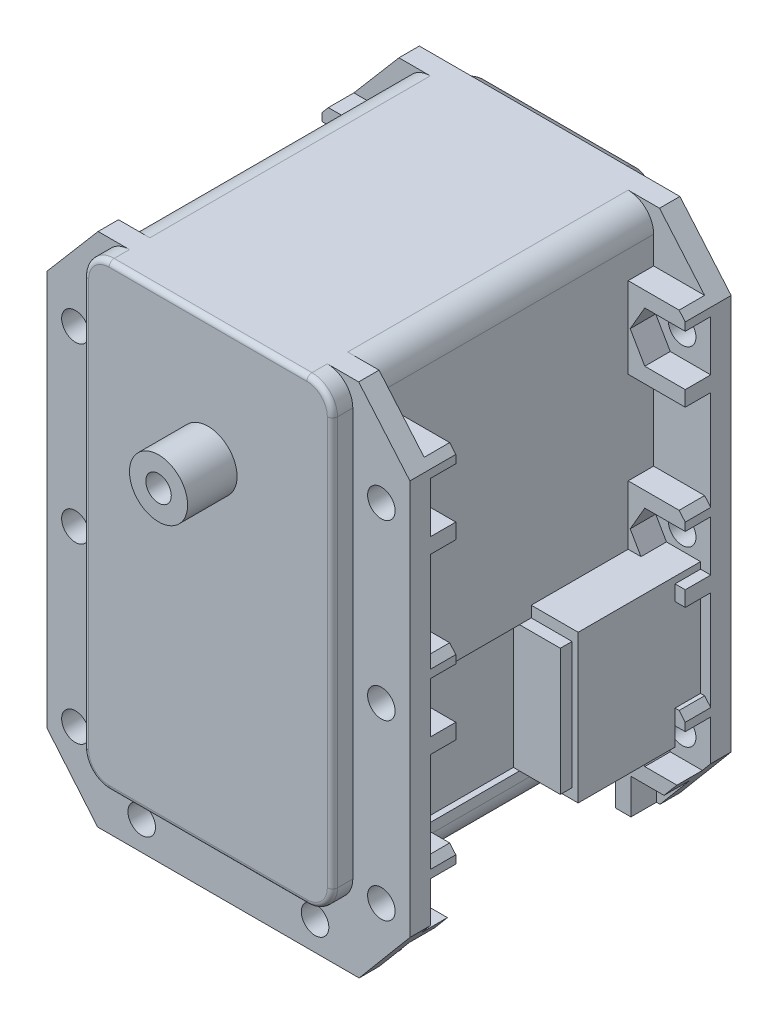
SolidWorks part; units mm, degrees
ref_plane "Ön Düzlem" through (0, 0, 0) normal (0, 0, 1) x (1, 0, 0)
ref_plane "Üst Düzlem" through (0, 0, 0) normal (0, 1, 0) x (1, 0, 0)
ref_plane "Sağ Düzlem" through (0, 0, 0) normal (1, 0, 0) x (0, 0, -1)
sketch "Sketch1" plane through (0, 0, 0) normal (0, 0, 1) x (1, 0, 0)
  line L1 (-12.2, 22.5) -> (12.2, 22.5)
  line L2 (-12.2, 22.5) -> (-12.2, -22.5)
  line L3 (-12.2, -22.5) -> (12.2, -22.5)
  line L4 (12.2, 22.5) -> (12.2, -22.5)
  line L5 (-12.2, 22.5) -> (12.2, -22.5) construction
  line L6 (-12.2, -22.5) -> (12.2, 22.5) construction
  point P0 (0, 0)
  dimension "D1" = 45
  dimension "D2" = 24.4
extrude "Boss-Extrude1" add sketch "Sketch1" along normal mid plane 35.5
ref_plane "Plane1" through (0, 0, 15.75) normal (0, 0, 1) x (1, 0, 0)
sketch "Sketch2" plane through (0, 0, 15.75) normal (0, 0, 1) x (1, 0, 0)
  line L1 (-12.7753, 22.5) -> (-17.8, 16.6036)
  line L2 (-17.8, 16.6036) -> (-17.8, -22.1655)
  line L3 (-17.8, -22.1655) -> (-12.8203, -28.1)
  line L4 (-12.8203, -28.1) -> (12.8203, -28.1)
  line L5 (12.8203, -28.1) -> (17.8, -22.1655)
  line L6 (17.8, -22.1655) -> (17.8, 16.6036)
  line L7 (17.8, 16.6036) -> (12.7753, 22.5)
  line L8 (12.7753, 22.5) -> (-12.7753, 22.5)
  line L9 (0, 0) -> (0, -28.1) construction
  line L10 (12.2, -22.5) -> (12.2, 22.5) construction
  line L11 (-12.2, -22.5) -> (12.2, -22.5) construction
  line L14 (12.2, 22.5) -> (-12.2, 22.5) construction
  circle A0 centre (15, 13.3345) radius 1.35
  circle A1 centre (15, -3.6655) radius 1.35
  circle A2 centre (15, -20.6655) radius 1.35
  circle A3 centre (8.5, -25.3) radius 1.35
  circle A4 centre (-8.5, -25.3) radius 1.35
  circle A5 centre (-15, -20.6655) radius 1.35
  circle A6 centre (-15, 13.3345) radius 1.35
  circle A7 centre (-15, -3.6655) radius 1.35
  dimension "D9" = 15
  dimension "D8" = 2.7
  dimension "D1" = 35.6
  dimension "D2" = 220
  dimension "D3" = 5.9345
  dimension "D4" = 5.6
  dimension "D5" = 17
  dimension "D6" = 17
  dimension "D7" = 220.437
  dimension "D10" = 8.5
  dimension "D11" = 1.5
  dimension "D12" = 2.8
extrude "Boss-Extrude2" add sketch "Sketch2" against normal blind 2 separate body
sketch "Sketch4" plane through (0, 0, 13.75) normal (0, 0, -1) x (-1, 0, 0)
  line L0 (12.2, 22.5) -> (12.2, -22.5) construction
  line L1 (17.8, 9.3595) -> (12.2, 9.3595)
  line L2 (17.8, 9.3595) -> (17.8, 17.3095)
  line L3 (17.8, 17.3095) -> (12.2, 17.3095)
  line L4 (12.2, 9.3595) -> (12.2, 17.3095)
  line L5 (17.8, 9.3595) -> (12.2, 17.3095) construction
  line L6 (17.8, 17.3095) -> (12.2, 9.3595) construction
  line L7 (17.8, 15.8095) -> (13.83, 15.8095)
  line L8 (13.83, 15.8095) -> (12.4, 13.3345)
  line L9 (12.4, 13.3345) -> (13.83, 10.8595)
  line L10 (13.83, 10.8595) -> (17.8, 10.8595)
  line L11 (15, 13.3345) -> (17.8, 13.3345) construction
  point P0 (15, 13.3345)
  point P6 (15, 13.3345)
  line M16 (17.8, -22.1655) -> (17.8, 16.6036)
  line M17 (17.8, 16.6036) -> (12.7753, 22.5)
  dimension "D1" = 7.95
  dimension "D2" = 4.95
  dimension "D3" = 1.43
  dimension "D4" = 0.2
extrude "Boss-Extrude6" add sketch "Sketch4" along normal blind 2.5 contours L10 L9 L8 L7 L2 L3 L4 L1 M17 M16 region at (-15, 9.4568, 13.75)
pattern_linear "LPattern1" count 3 spacing 17 along (0, -1, 0) of "Boss-Extrude6"
sketch "Sketch6" plane through (0, 0, 13.75) normal (0, 0, -1) x (-1, 0, 0)
  line L0 (12.8203, -28.1) -> (-12.8203, -28.1) construction
  line L1 (12.475, -22.5) -> (4.525, -22.5)
  line L2 (12.475, -22.5) -> (12.475, -28.1)
  line L3 (12.475, -28.1) -> (4.525, -28.1)
  line L4 (4.525, -22.5) -> (4.525, -28.1)
  line L5 (12.475, -22.5) -> (4.525, -28.1) construction
  line L6 (12.475, -28.1) -> (4.525, -22.5) construction
  line L7 (10.975, -28.1) -> (10.975, -24.13)
  line L8 (10.975, -24.13) -> (8.5, -22.7)
  line L9 (8.5, -22.7) -> (6.025, -24.13)
  line L10 (6.025, -24.13) -> (6.025, -28.1)
  line L11 (8.5, -25.3) -> (8.5, -28.1) construction
  point P0 (8.5, -25.3)
  line M6 (15.7232, -24.6405) -> (12.2, -24.6405)
  line M7 (12.2, -24.6405) -> (12.2, -16.6905)
  line M14 (-12.8203, -28.1) -> (12.8203, -28.1)
  dimension "D1" = 7.95
  dimension "D2" = 4.95
  dimension "D3" = 0.2
  dimension "D4" = 1.43
extrude "Boss-Extrude7" add sketch "Sketch6" along normal up to surface (2.5 mm away) contours L2 L1 M7 M6 | L10 L9 L8 L7 L3 L2 L1 L4 M6 M7 M14 region at (-12.3375, -23.5702, 13.75) region at (-12.1028, -23.5702, 13.75)
mirror "Mirror1" about plane through (0, 0, 0) normal (1, 0, 0) of "Boss-Extrude6", "LPattern1", "Boss-Extrude7"
sketch "Sketch7" plane through (0, 0, 15.75) normal (0, 0, 1) x (1, 0, 0)
  line L0 (12.7753, 22.5) -> (24.5744, 22.5)
  line L1 (24.5744, 22.5) -> (23.5636, -35.3493)
  line L2 (23.5636, -35.3493) -> (-23.3668, -35.3493)
  line L3 (-23.3668, -35.3493) -> (-23.3668, 22.5)
  line L4 (-23.3668, 22.5) -> (-12.7753, 22.5)
  line L8 (12.7753, 22.5) -> (-12.7753, 22.5)
  line L9 (-12.7753, 22.5) -> (-17.8, 16.6036)
  line L10 (-17.8, 16.6036) -> (-17.8, -22.1655)
  line L11 (-17.8, -22.1655) -> (-12.8203, -28.1)
  line L12 (-12.8203, -28.1) -> (12.8203, -28.1)
  line L13 (12.8203, -28.1) -> (17.8, -22.1655)
  line L14 (17.8, -22.1655) -> (17.8, 16.6036)
  line L15 (17.8, 16.6036) -> (12.7753, 22.5)
  line L16 (12.7753, 22.5) -> (-12.7753, 22.5)
  line L17 (-12.7753, 22.5) -> (-17.8, 16.6036)
  line L18 (-17.8, 16.6036) -> (-17.8, -22.1655)
  line L19 (-17.8, -22.1655) -> (-12.8203, -28.1)
  line L20 (-12.8203, -28.1) -> (12.8203, -28.1)
  line L21 (12.8203, -28.1) -> (17.8, -22.1655)
  line L22 (17.8, -22.1655) -> (17.8, 16.6036)
  line L23 (17.8, 16.6036) -> (12.7753, 22.5)
  line M18 (-12.7753, 22.5) -> (-17.8, 16.6036)
  line M19 (-17.8, 16.6036) -> (-17.8, -22.1655)
  line M20 (-17.8, -22.1655) -> (-12.8203, -28.1)
  line M21 (-12.8203, -28.1) -> (12.8203, -28.1)
  line M22 (12.8203, -28.1) -> (17.8, -22.1655)
  line M23 (17.8, -22.1655) -> (17.8, 16.6036)
  line M24 (17.8, 16.6036) -> (12.7753, 22.5)
  dimension "D1" = 0
extrude "Cut-Extrude1" cut sketch "Sketch7" against normal through all contours L4 L3 L2 L1 L0 M24 M23 M22 M21 M20 M19 M18 region at (18.6748, 21.7487, 15.75)
mirror "Mirror2" about plane through (0, 0, 0) normal (0, 0, 1) of bodies 108
sketch "Sketch8" plane through (0, 0, 17.75) normal (0, 0, 1) x (1, 0, 0)
  line L0 (12.2, 22.5) -> (-12.2, 22.5) construction
  circle A0 centre (0, 10.5) radius 2.85
  dimension "D1" = 5.7
  dimension "D2" = 12
extrude "Boss-Extrude8" add sketch "Sketch8" along normal blind 4.85
fillet "Fillet1" radius 2.5 4 edges at (12.2, 22.5, 0) (-12.2, 22.5, 0) (-12.2, -22.5, 0) (12.2, -22.5, 0)
ref_plane "Plane2" through (0, 10.5, 0) normal (0, 1, 0) x (1, 0, 0)
sketch "Sketch11" plane through (0, 10.5, 0) normal (0, 1, 0) x (1, 0, 0)
  line L0 (0, 0) -> (0, 28.343) construction
  line L2 (3.3693, 16.65) -> (0, 16.65)
  line L3 (3.3693, 16.65) -> (4, 16.65)
  line L4 (4, 16.65) -> (4, 16.35)
  line L5 (4, 16.35) -> (6.5, 16.35)
  line L6 (6.5, 16.35) -> (6.5, 19.25)
  line L7 (6.5, 19.25) -> (0, 19.25)
  line L8 (0, 16.65) -> (0, 19.25)
  line L11 (9.7, 17.75) -> (-9.7, 17.75) construction
  dimension "D1" = 1.5
  dimension "D2" = 1.4
  dimension "D3" = 0.3
  dimension "D4" = 6.5
  dimension "D5" = 4
revolve "Cut-Revolve1" cut sketch "Sketch11" angle 360 about L0
sketch "Sketch12" plane through (0, 0, -16.65) normal (0, 0, -1) x (-1, 0, 0)
  circle A0 centre (0, 10.5) radius 3
  circle A1 centre (0, 10.5) radius 4 construction
  circle A2 centre (0, 10.5) radius 1.6
  dimension "D1" = 6
  dimension "D2" = 3.2
extrude "Boss-Extrude10" add sketch "Sketch12" along normal offset from surface (2.6 mm away) 1.5 up to face at (6.5, 10.5, -17.75) offset beyond the face yes
combine bodies "Combine1" operation type add bodies to combine 113 108 109
sketch "Sketch13" plane through (0, 0, -17.75) normal (0, 0, -1) x (-1, 0, 0)
  line L2 (-11.4678, 21.7678) -> (0, 10.5) construction
  line L3 (-10.0409, 18.3658) -> (-12.2, 18.3658)
  line L4 (-12.2, -20) -> (-12.2, 20) construction
  line L5 (-8.0409, 28.327) -> (-8.0409, 20.3658)
  line L6 (-12.2, 28.327) -> (-8.0409, 28.327)
  line L7 (-12.2, 18.3658) -> (-12.2, 28.327)
  circle A0 centre (-10.0409, 20.3658) radius 2
  arc A1 (-9.7, 22.5) -> (-12.2, 20) centre (-9.7, 20) ccw construction
  line M2 (9.7, 22.5) -> (-9.7, 22.5)
  arc M3 (-9.7, 22.5) -> (-12.2, 20) centre (-9.7, 20) ccw
  line M4 (-12.2, 20) -> (-12.2, -20)
  dimension "D1" = 4
extrude "Cut-Extrude2" cut sketch "Sketch13" against normal up to surface (2 mm away) contours A0 L5 M2 M3 | A0 L2 | L2 A0 | L2 L3 A0 M3 M4 | L7 L5 L6 M3 M2 | L2 A0 M3 region at (11.452, 21.7831, -17.75) region at (11.7519, 19.0665, -17.75) region at (10.2002, 25.2314, -17.75) region at (9.446, 20.9712, -17.75) region at (10.6358, 19.7603, -17.75) region at (8.7026, 22.055, -17.75) up to face at (-16.35, -3.6655, -15.75)
mirror "Mirror3" about plane through (0, 0, 0) normal (1, 0, 0) of "Cut-Extrude2"
mirror "Mirror4" about plane through (0, 0, 0) normal (0, 1, 0) of "Mirror3"
sketch "Sketch14" plane through (-12.2, 0, 0) normal (-1, 0, 0) x (0, 0, 1)
  line L0 (-17.75, 20.3658) -> (-17.75, 18.3658) construction
  line L1 (-17.75, 19.3377) -> (-17.75, 23.5276) construction
  line L2 (-17.75, 18.3658) -> (-17.75, -18.3658) construction
  line L3 (-15.75, 22.5) -> (-18.3843, 22.5)
  line L4 (-18.3843, 22.5) -> (-18.3843, 19.3377)
  line L5 (-18.3843, 19.3377) -> (-17.75, 19.3377)
  arc A0 (-17.75, 19.3377) -> (-15.75, 22.5) centre (-14.25, 19.3377) cw
  dimension "D1" = 3.5
extrude "Cut-Extrude3" cut sketch "Sketch14" against normal through all
sketch "Sketch15" plane through (-12.2, 0, 0) normal (-1, 0, 0) x (0, 0, 1)
  line L0 (-13.75, -7.6405) -> (-13.75, -17.3964) construction
  line L1 (-13.75, -6.58) -> (13.75, -6.58)
  line L2 (-13.75, -6.58) -> (-13.75, -19)
  line L3 (-13.75, -19) -> (13.75, -19)
  line L4 (13.75, -6.58) -> (13.75, -19)
  line L5 (-13.75, -6.58) -> (13.75, -19) construction
  line L6 (-13.75, -19) -> (13.75, -6.58) construction
  line L7 (13.75, -7.6405) -> (13.75, -17.3964) construction
  line L8 (-11.25, -20) -> (11.25, -20) construction
  point P0 (0, -12.79)
  dimension "D1" = 12.42
  dimension "D2" = 1
extrude "Cut-Extrude4" cut sketch "Sketch15" against normal blind 0.6
sketch "Sketch16" plane through (-11.6, 0, 0) normal (-1, 0, 0) x (0, 0, 1)
  line L0 (-13.75, -7.6405) -> (-13.75, -17.3964) construction
  line L1 (-13.75, -5.5) -> (-1.75, -5.5)
  line L2 (-13.75, -5.5) -> (-13.75, -20)
  line L3 (-13.75, -20) -> (-1.75, -20)
  line L4 (-1.75, -5.5) -> (-1.75, -20)
  line L5 (-13.75, -5.5) -> (-1.75, -20) construction
  line L6 (-13.75, -20) -> (-1.75, -5.5) construction
  line L8 (-11.25, -20) -> (11.25, -20) construction
  line L10 (-11.25, -20) -> (-11.25, -17.3964)
  line L11 (-11.25, -17.3964) -> (-13.75, -17.3964)
  point P0 (-7.75, -12.75)
  line M2 (13.75, -6.58) -> (-13.75, -6.58)
  line M3 (-13.75, -6.58) -> (-13.75, -19)
  line M4 (-13.75, -19) -> (13.75, -19)
  dimension "D1" = 14.5
  dimension "D2" = 12
extrude "Boss-Extrude11" add sketch "Sketch16" along normal offset from surface (5.2 mm away) 4.6 separate body contours L4 L1 L2 M2 | L10 L3 L4 M4 | L11 L10 L4 M4 M2 M3 region at (-11.6, -6.04, -7.75) region at (-11.6, -12.6405, -7.6187) region at (-11.6, -19.5, -6.5) up to face at (-12.2, 8.4221, 0) offset beyond the face yes
sketch "Sketch17" plane through (-11.6, 0, 0) normal (-1, 0, 0) x (0, 0, 1)
  line L0 (-13.75, -19) -> (13.75, -19) construction
  line L1 (-1.75, -6.58) -> (-0.6, -6.58)
  line L2 (-1.75, -6.58) -> (-1.75, -19)
  line L3 (-1.75, -19) -> (-0.6, -19)
  line L4 (-0.6, -6.58) -> (-0.6, -19)
  line L5 (-1.75, -6.58) -> (-0.6, -19) construction
  line L6 (-1.75, -19) -> (-0.6, -6.58) construction
  line L7 (11.25, -6.58) -> (-11.25, -6.58) construction
  line L9 (-13.75, -7.6405) -> (-13.75, -17.3964) construction
  point P0 (-1.175, -12.79)
  dimension "D1" = 1.15
  dimension "D2" = 12
extrude "Boss-Extrude12" add sketch "Sketch17" along normal blind 4.6
mirror "Mirror11" about plane through (0, 0, 0) normal (1, 0, 0) of "Cut-Extrude4"
mirror "Mirror10" about plane through (0, 0, 0) normal (1, 0, 0) of bodies 121
combine bodies "Combine2" operation type add bodies to combine 124 123 121
fillet "Fillet3" radius 1.5 6 edges at (-12.2, 18.3658, -16.75) (12.2, 18.3658, -16.75) (8.0409, -22.5, -16.75) (12.2, -18.3658, -16.75) (-12.2, -18.3658, -16.75) (-8.0409, -22.5, -16.75)
fillet "Fillet4" radius 0.5 31 edges at (12.2, 0, 17.75) (11.4678, -21.7678, 17.75) (0, -22.5, 17.75) (-11.4678, -21.7678, 17.75) (-12.2, 0, 17.75) (-11.4678, 21.7678, 17.75) (0, 22.5, 17.75) (-8.0409, 21.6271, -16.8974) (-8.0974, 19.8937, -17.7056) (-9.055, 18.6256, -17.75) (-10.3704, 18.3658, -17.75) (-11.7607, 17.9264, -17.75) (8.0409, 21.6271, -16.8974) (8.0974, 19.8937, -17.7056) (9.055, 18.6256, -17.75) (10.3704, 18.3658, -17.75) (11.7607, 17.9264, -17.75) (12.2, 0, -17.75) (11.7607, -17.9264, -17.75) (10.3704, -18.3658, -17.75) (8.6267, -18.9516, -17.75) (8.0409, -20.6829, -17.75) (7.6016, -22.0607, -17.75) (0, -22.5, -17.75) (-7.6016, -22.0607, -17.75) (-8.0409, -20.6829, -17.75) (-8.6267, -18.9516, -17.75) (-10.3704, -18.3658, -17.75) (-11.7607, -17.9264, -17.75) (11.4678, 21.7678, 17.75) (-12.2, 0, -17.75)
ref_axis "Axis1" through (8.5, -25.3, 13.75) along (0, 0, 1)
ref_axis "Axis2" through (0, 10.5, -19.25) along (0, 0, 1)
sketch "Sketch19" plane through (0, 0, 22.6) normal (0, 0, 1) x (1, 0, 0)
  circle A0 centre (0, 10.5) radius 1.25
  dimension "D1" = 2.5
extrude "Cut-Extrude5" cut sketch "Sketch19" against normal blind 10
